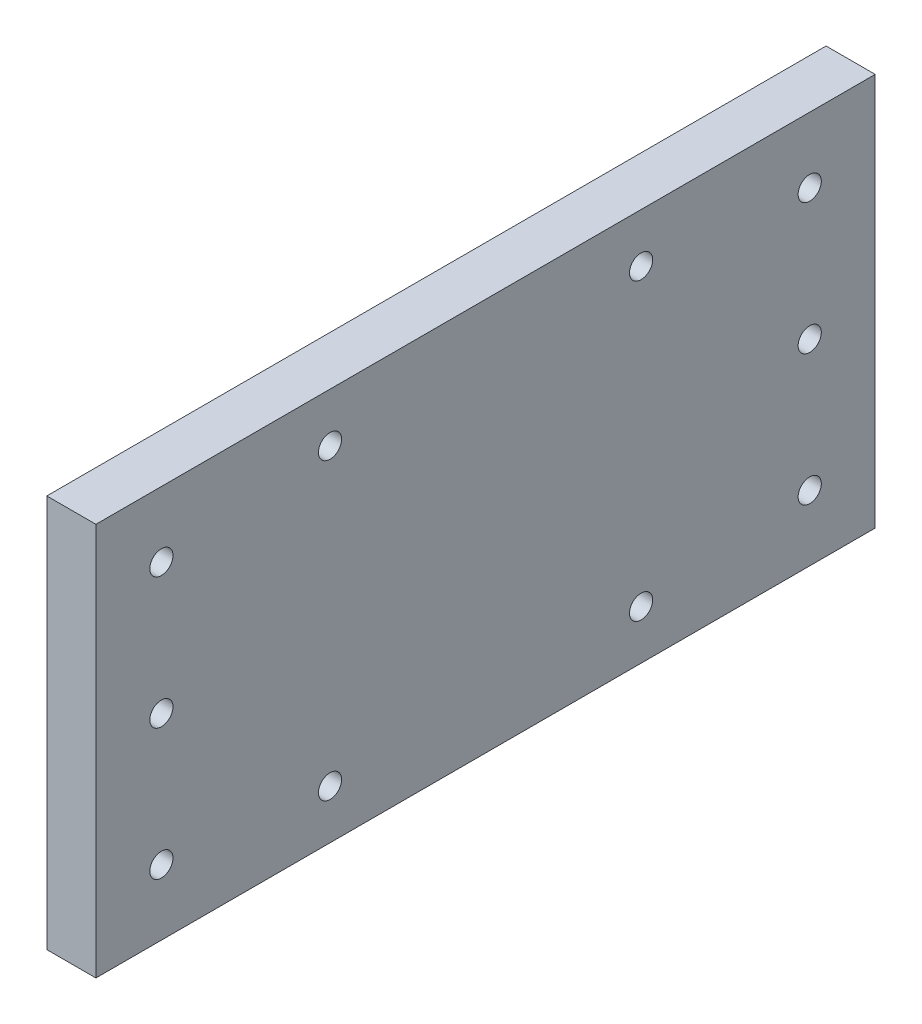
SolidWorks part; units mm, degrees
material "AISI 1015 Steel, Cold Drawn (SS)"
ref_plane "Front Plane" through (0, 0, 0) normal (0, 0, 1) x (1, 0, 0)
ref_plane "Top Plane" through (0, 0, 0) normal (0, 1, 0) x (1, 0, 0)
ref_plane "Right Plane" through (0, 0, 0) normal (1, 0, 0) x (0, 0, -1)
sketch "Sketch1" plane through (0, 0, 0) normal (0, 0, 1) x (1, 0, 0)
  line L1 (-4.7625, 38.1) -> (4.7625, 38.1)
  line L2 (-4.7625, 38.1) -> (-4.7625, -38.1)
  line L3 (-4.7625, -38.1) -> (4.7625, -38.1)
  line L4 (4.7625, 38.1) -> (4.7625, -38.1)
  line L5 (-4.7625, 38.1) -> (4.7625, -38.1) construction
  line L6 (-4.7625, -38.1) -> (4.7625, 38.1) construction
  point P0 (0, 0)
  dimension "D1" = 9.525
  dimension "D2" = 76.2
extrude "Boss-Extrude1" add sketch "Sketch1" along normal blind 151.13
hole_wizard "#8 Clearance Hole1" positions "Sketch3" profile "Sketch2" hole size "#8" standard "ANSI Inch" end condition through all
sketch "Sketch3" plane through (4.7625, 0, 0) normal (1, 0, 0) x (0, 0, -1)
  line L1 (-105.7275, 28.575) -> (-45.4025, 28.575)
  line L2 (-105.7275, 28.575) -> (-105.7275, -28.575)
  line L3 (-105.7275, -28.575) -> (-45.4025, -28.575)
  line L4 (-45.4025, 28.575) -> (-45.4025, -28.575)
  line L5 (-105.7275, 28.575) -> (-45.4025, -28.575) construction
  line L6 (-105.7275, -28.575) -> (-45.4025, 28.575) construction
  line L7 (0, 0) -> (-75.565, 0) construction
  line L9 (-75.565, 38.1) -> (-75.565, 0) construction
  line L10 (-151.13, 38.1) -> (0, 38.1) construction
  point P2 (-45.4025, -28.575)
  point P55 (-105.7275, 28.575)
  point P56 (-105.7275, -28.575)
  point P57 (-45.4025, 28.575)
  dimension "D1" = 60.325
  dimension "D2" = 57.15
sketch "Sketch2" plane through (4.7625, -28.575, 45.4025) normal (0, 1, 0) x (0, 0, -1)
  line L0 (0, 0) -> (0, 9.525)
  line L1 (0, 9.525) -> (2.2479, 9.525)
  line L2 (2.2479, 9.525) -> (2.2479, 0)
  line L5 (2.2479, 0) -> (0, 0)
  line L11 (0, -6.35) -> (0, 107.95) construction
  dimension "Thru Hole Dia." = 4.4958
  dimension "Thru Hole Depth" = 9.525
hole_wizard "#8 Clearance Hole2" positions "Sketch5" profile "Sketch4" hole size "#8" standard "ANSI Inch" end condition through all
sketch "Sketch5" plane through (4.7625, 0, 0) normal (1, 0, 0) x (0, 0, -1)
  line L0 (-151.13, -38.1) -> (-151.13, 38.1) construction
  line L1 (-151.13, -38.1) -> (0, -38.1) construction
  line L2 (0, -38.1) -> (0, 38.1) construction
  point P0 (-138.43, 25.4)
  point P2 (-138.43, 0)
  point P4 (-138.43, -25.4)
  point P6 (-12.7, 25.4)
  point P8 (-12.7, 0)
  point P10 (-12.7, -25.4)
  dimension "D1" = 12.7
  dimension "D2" = 25.4
  dimension "D3" = 25.4
  dimension "D4" = 12.7
  dimension "D5" = 12.7
sketch "Sketch4" plane through (4.7625, 25.4, 138.43) normal (0, 1, 0) x (0, 0, -1)
  line L0 (0, 0) -> (0, 9.525)
  line L1 (0, 9.525) -> (2.2479, 9.525)
  line L2 (2.2479, 9.525) -> (2.2479, 0)
  line L5 (2.2479, 0) -> (0, 0)
  line L11 (0, -6.35) -> (0, 107.95) construction
  dimension "Thru Hole Dia." = 4.4958
  dimension "Thru Hole Depth" = 9.525
